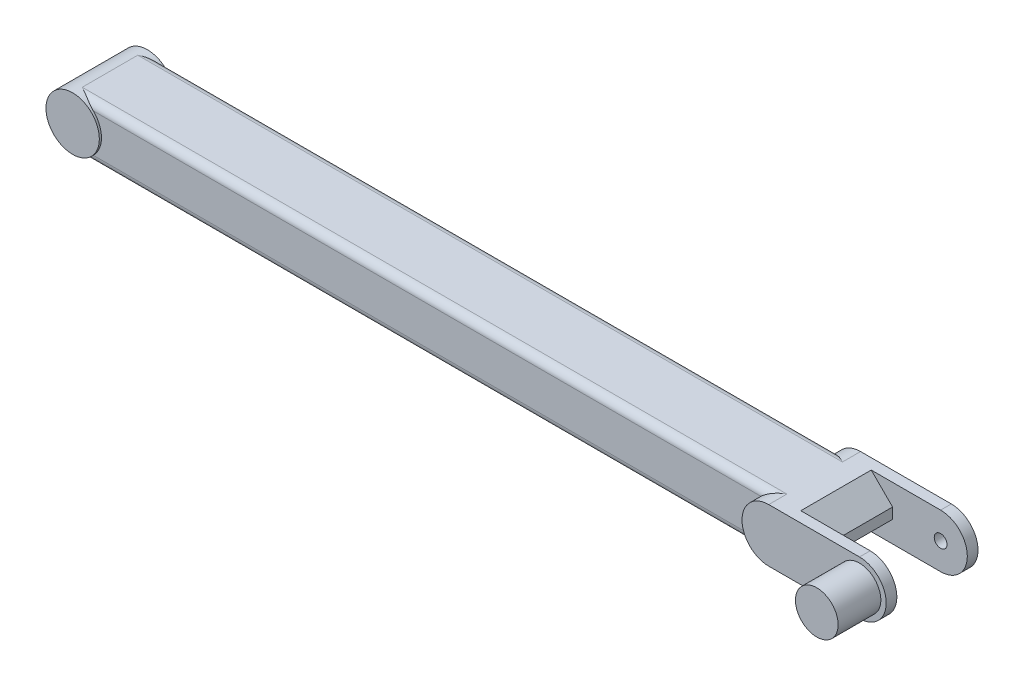
SolidWorks part; units mm, degrees
material "Thornel Mat VMA"
ref_plane "Ebene vorne" through (0, 0, 0) normal (0, 0, 1) x (1, 0, 0)
ref_plane "Ebene oben" through (0, 0, 0) normal (0, 1, 0) x (1, 0, 0)
ref_plane "Ebene rechts" through (0, 0, 0) normal (1, 0, 0) x (0, 0, -1)
sketch "Skizze1" plane through (0, 0, 0) normal (0, 0, 1) x (1, 0, 0)
  circle A0 centre (0, 0) radius 25
  dimension "D1" = 50
extrude "Aufsatz-Linear austragen1" add sketch "Skizze1" along normal blind 35 and the other way blind 35
sketch "Skizze2" plane through (0, 0, 0) normal (1, 0, 0) x (0, 0, -1)
  line L1 (-33, 25) -> (33, 25)
  line L2 (-33, 25) -> (-33, -25)
  line L3 (-33, -25) -> (33, -25)
  line L4 (33, 25) -> (33, -25)
  point P4 (0, 25)
  point P6 (-33, 0)
  dimension "D1" = 66
  dimension "D2" = 50
extrude "Aufsatz-Linear austragen2" add sketch "Skizze2" along normal blind 700
sketch "Skizze3" plane through (0, 0, -33) normal (0, 0, -1) x (-1, 0, 0)
  line L0 (-700, 25) -> (-660, 25)
  line L1 (-700, 25) -> (0, 25) construction
  line L2 (-700, -25) -> (-660, -25)
  line L3 (-700, -25) -> (0, -25) construction
  line L4 (-700, 25) -> (-745, 25)
  line L5 (-700, -25) -> (-745, -25)
  arc A0 (-660, 25) -> (-660, -25) centre (-660, 0) cw
  arc A1 (-745, 25) -> (-745, -25) centre (-745, 0) ccw
  dimension "D1" = 40
  dimension "D2" = 45
extrude "Aufsatz-Linear austragen3" add sketch "Skizze3" along normal blind 10
sketch "Skizze4" plane through (0, 0, -43) normal (0, 0, -1) x (-1, 0, 0)
  line L0 (-700, 25) -> (-700, -25) construction
  circle A1 centre (-745, 0) radius 6
  dimension "D1" = 45
extrude "Schnitt-Linear austragen1" cut sketch "Skizze4" against normal up to next
mirror "Spiegeln1" about plane through (0, 0, 0) normal (0, 0, 1) of "Aufsatz-Linear austragen3", "Schnitt-Linear austragen1"
fillet "Verrundung2" radius 7 4 edges at (330, -25, -33) (330, 25, -33) (330, -25, 33) (330, 25, 33)
chamfer "Fase1" distance 20 distance2 20 2 edges at (700, -25, 0) (700, 25, 0)
sketch "Skizze5" plane through (0, 0, 43) normal (0, 0, 1) x (1, 0, 0)
  circle A0 centre (745, 0) radius 20
extrude "Aufsatz-Linear austragen4" add sketch "Skizze5" along normal blind 40
